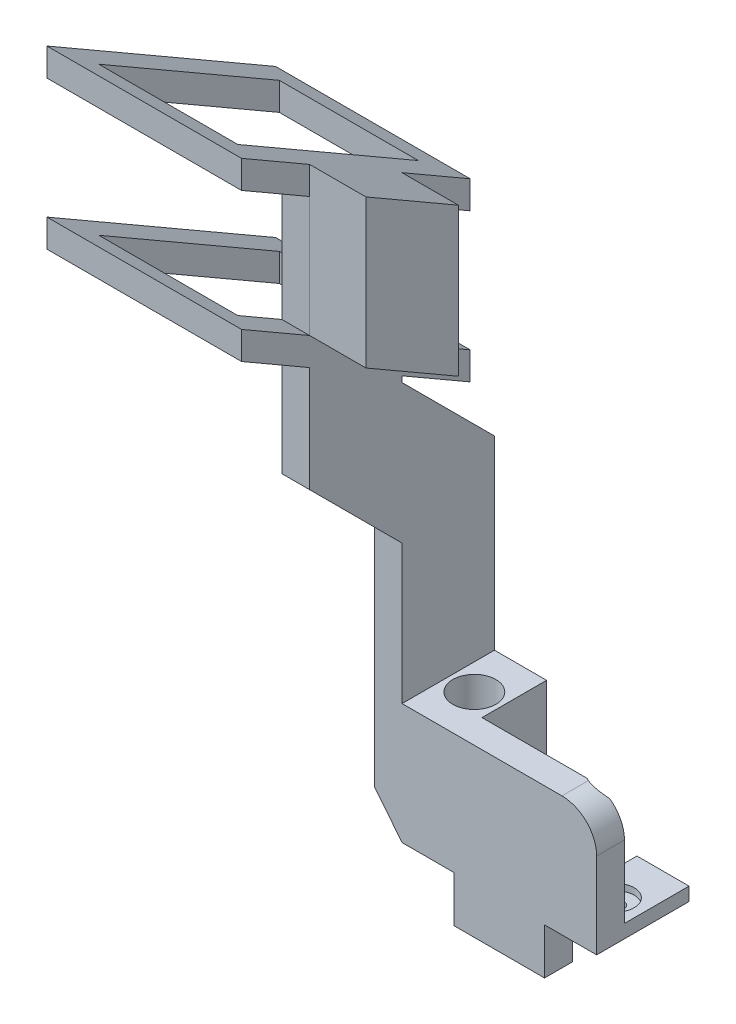
SolidWorks part; units mm, degrees
ref_plane "Front Plane" through (0, 0, 0) normal (0, 0, 1) x (1, 0, 0)
ref_plane "Top Plane" through (0, 0, 0) normal (0, 1, 0) x (1, 0, 0)
ref_plane "Right Plane" through (0, 0, 0) normal (1, 0, 0) x (0, 0, -1)
sketch "Sketch1" plane through (0, 0, 0) normal (0, 1, 0) x (1, 0, 0)
  line L1 (2.6118, 0) -> (10.109, 0)
  line L2 (2.6118, 0) -> (2.6118, -13.3)
  line L3 (2.6118, -13.3) -> (10.109, -13.3)
  line L4 (10.109, 0) -> (10.109, -13.3)
  line L5 (23.1146, -13.3) -> (30.6118, -13.3)
  line L6 (23.1146, -13.3) -> (23.1146, 0)
  line L7 (23.1146, 0) -> (30.6118, 0)
  line L8 (30.6118, -13.3) -> (30.6118, 0)
  circle A0 centre (6.3604, -6.65) radius 1
  circle A1 centre (26.8632, -6.65) radius 1
  point P20 (6.3604, 0)
  point P21 (2.6118, -6.65)
  point P22 (26.8632, 0)
  point P23 (30.6118, -6.65)
  dimension "D1" = 2
  dimension "D2" = 2
extrude "Boss-Extrude1" add sketch "Sketch1" along normal blind 2
sketch "Sketch2" plane through (0, 2, 0) normal (0, 1, 0) x (1, 0, 0)
  line L1 (2.6118, -13.3) -> (10.109, -13.3)
  line L2 (2.6118, -13.3) -> (2.6118, 0)
  line L3 (2.6118, 0) -> (10.109, 0)
  line L4 (10.109, -13.3) -> (10.109, 0)
sketch "Sketch3" plane through (0, 2, 0) normal (0, 1, 0) x (1, 0, 0)
  circle A0 centre (26.8632, -6.65) radius 2.5
  circle A1 centre (6.3604, -6.65) radius 2.5
  dimension "D1" = 5
  dimension "D2" = 5
extrude "Cut-Extrude1" cut sketch "Sketch3" against normal blind 1
sketch "Sketch4" plane through (0, 0, 13.3) normal (0, 0, 1) x (1, 0, 0)
  line L0 (10.109, 0) -> (10.109, -6.6258)
  line L1 (10.109, -6.6258) -> (23.1146, -6.6258)
  line L2 (23.1146, -6.6258) -> (23.1146, 2)
  line L3 (23.1146, 2) -> (10.109, 2)
  line L4 (10.109, 2) -> (10.109, 0)
extrude "Boss-Extrude3" add sketch "Sketch4" against normal blind 1
sketch "Sketch5" plane through (0, 2, 0) normal (0, 1, 0) x (1, 0, 0)
  line L0 (2.6118, 0) -> (2.6118, -13.3) construction
  line L1 (10.109, 0) -> (2.6118, 0)
  line L2 (10.109, 0) -> (10.109, -4)
  line L4 (2.6118, 0) -> (2.6118, -4)
  line L5 (23.1146, -12.3) -> (10.109, -12.3) construction
  line L6 (30.6118, -13.3) -> (2.6118, -13.3)
  line L7 (30.6118, -13.3) -> (30.6118, -12.3)
  line L8 (23.1146, -12.3) -> (10.109, -12.3)
  line L9 (2.6118, -13.3) -> (2.6118, -12.3)
  line L10 (10.109, -12.3) -> (10.109, 0) construction
  line L12 (2.6118, -12.3) -> (2.6118, -9.3)
  line L14 (10.109, -12.3) -> (10.109, -9.3)
  line L15 (30.6118, -13.3) -> (30.6118, 0) construction
  line L17 (23.1146, -12.3) -> (23.1146, -9.3)
  line L19 (30.6118, -12.3) -> (30.6118, -9.3)
  line L20 (23.1146, 0) -> (23.1146, -12.3) construction
  line L21 (30.6118, 0) -> (23.1146, 0)
  line L22 (30.6118, 0) -> (30.6118, -4)
  line L24 (23.1146, 0) -> (23.1146, -4)
  line L25 (2.6118, -4) -> (2.6118, -9.3)
  line L26 (10.109, -4) -> (10.109, -9.3)
  line L27 (23.1146, -4) -> (23.1146, -9.3)
  line L28 (30.6118, -4) -> (30.6118, -9.3)
  circle A0 centre (6.3604, -6.65) radius 3.1
  circle A1 centre (26.8632, -6.65) radius 3.1
  dimension "D5" = 6.2
  dimension "D6" = 6.2
  dimension "D1" = 4
  dimension "D2" = 3
  dimension "D3" = 3
  dimension "D4" = 4
extrude "Boss-Extrude4" add sketch "Sketch5" along normal up to surface (15.3233 mm away)
sketch "Sketch6" plane through (30.6118, 0, 0) normal (1, 0, 0) x (0, 0, -1)
  line L3 (-9.3, 17.3233) -> (0, 17.3233)
  line L5 (0, 17.3233) -> (0, 0) construction
  line L7 (0, 3.9257) -> (-9.3, 3.9257)
  line L8 (-9.3, 17.3233) -> (-9.3, 3.9257)
  line L10 (0, 17.3233) -> (0, 3.9257)
extrude "Cut-Extrude2" cut sketch "Sketch6" against normal up to surface (7.4972 mm away) up to face at (23.1146, 8.6616, 6.15)
sketch "Sketch7" plane through (0, 17.3233, 0) normal (0, 1, 0) x (1, 0, 0)
  line L0 (28.4718, -9.3) -> (30.6118, -9.3)
  line L1 (10.109, -13.3) -> (30.6118, -13.3)
  line L2 (10.109, -13.3) -> (10.109, -9.3)
  line L3 (10.109, -9.3) -> (25.2546, -9.3)
  line L4 (30.6118, -13.3) -> (30.6118, -9.3)
  arc A0 (25.2546, -9.3) -> (28.4718, -9.3) centre (26.8632, -6.65) ccw
extrude "Boss-Extrude5" add sketch "Sketch7" against normal up to surface (13.3976 mm away) up to face at (26.8632, 3.9257, 5.2417)
sketch "Sketch8" plane through (0, 3.9257, 0) normal (0, -1, 0) x (1, 0, 0)
  line L1 (10.109, 9.3) -> (23.1146, 9.3)
  line L2 (10.109, 9.3) -> (10.109, 12.3)
  line L3 (10.109, 12.3) -> (23.1146, 12.3)
  line L4 (23.1146, 9.3) -> (23.1146, 12.3)
extrude "Boss-Extrude6" add sketch "Sketch8" along normal through all
sketch "Sketch9" plane through (2.6118, 0, 0) normal (-1, 0, 0) x (0, 0, 1)
  line L0 (13.3, 17.3233) -> (13.3, 0) construction
  line L1 (0, 17.3233) -> (13.3, 17.3233)
  line L2 (0, 17.3233) -> (0, 5)
  line L3 (0, 5) -> (13.3, 5)
  line L4 (13.3, 17.3233) -> (13.3, 5)
  line L5 (0, 0) -> (13.3, 0) construction
  dimension "D1" = 5
extrude "Boss-Extrude7" add sketch "Sketch9" along normal blind 4
sketch "Sketch10" plane through (0, 17.3233, 0) normal (0, 1, 0) x (1, 0, 0)
  line L1 (-1.3882, 0) -> (2.6118, 0)
  line L2 (-1.3882, 0) -> (-1.3882, -13.3)
  line L3 (-1.3882, -13.3) -> (2.6118, -13.3)
  line L4 (2.6118, 0) -> (2.6118, -13.3)
extrude "Boss-Extrude8" add sketch "Sketch10" along normal blind 70
sketch "Sketch11" plane through (0, 0, 13.3) normal (0, 0, 1) x (1, 0, 0)
  line L0 (-1.3882, 5) -> (2.6118, 0)
  line L1 (2.6118, 0) -> (2.6118, 5)
  line L2 (2.6118, 5) -> (-1.3882, 5)
extrude "Boss-Extrude9" add sketch "Sketch11" against normal up to surface (13.3 mm away) up to face at (3.4861, 27.4116, 0)
sketch "Sketch15" plane through (0, 0, 13.3) normal (0, 0, 1) x (1, 0, 0)
  line L0 (-1.3882, 5) -> (-1.3882, 87.3233) construction
  line L1 (-1.3882, 57.3233) -> (2.6118, 57.3233)
  line L2 (-1.3882, 57.3233) -> (-1.3882, 37.3233)
  line L3 (-1.3882, 37.3233) -> (2.6118, 37.3233)
  line L4 (2.6118, 57.3233) -> (2.6118, 37.3233)
  line L5 (2.6118, 87.3233) -> (2.6118, 17.3233) construction
  line L6 (-1.3882, 87.3233) -> (2.6118, 87.3233) construction
  dimension "D1" = 20
  dimension "D2" = 30
extrude "Boss-Extrude13" add sketch "Sketch15" along normal blind 20
sketch "Sketch16" plane through (0, 57.3233, 0) normal (0, 1, 0) x (1, 0, 0)
  line L1 (-1.3882, -13.3) -> (2.6118, -13.3)
  line L2 (-1.3882, -13.3) -> (-1.3882, -33.3)
  line L3 (-1.3882, -33.3) -> (2.6118, -33.3)
  line L4 (2.6118, -13.3) -> (2.6118, -33.3)
extrude "Boss-Extrude14" add sketch "Sketch16" along normal up to surface (30 mm away) up to face at (0.6118, 87.3233, 6.65)
sketch "Sketch17" plane through (-1.3882, 0, 0) normal (-1, 0, 0) x (0, 0, 1)
  line L1 (0, 87.3233) -> (13.3, 87.3233)
  line L2 (0, 87.3233) -> (0, 57.3233)
  line L4 (13.3, 87.3233) -> (13.3, 57.3233)
  line L5 (0, 87.3233) -> (33.3, 87.3233) construction
  line L6 (33.3, 37.3233) -> (26.6, 37.3233)
  line L7 (33.3, 37.3233) -> (33.3, 87.3233)
  line L8 (33.3, 87.3233) -> (26.6, 87.3233)
  line L9 (26.6, 50.6233) -> (26.6, 87.3233)
  line L11 (13.3, 5) -> (13.3, 37.3233) construction
  line L12 (13.3, 57.3233) -> (63.724, 57.3233) construction
  line L13 (33.3, 37.3233) -> (-38.679, 37.3233) construction
  line L14 (13.3, 37.3233) -> (26.6, 50.6233)
  line L15 (13.3, 57.3233) -> (0, 44.0233)
  line L16 (0, 87.3233) -> (0, 5) construction
  line L17 (0, 57.3233) -> (0, 44.0233)
  line L18 (13.3, 37.3233) -> (33.3, 37.3233)
  line M13 (33.3, 37.3233) -> (33.3, 87.3233)
  line M14 (33.3, 87.3233) -> (0, 87.3233)
  line M15 (0, 87.3233) -> (0, 5)
  line M18 (13.3, 37.3233) -> (33.3, 37.3233)
  dimension "D2" = 13.3
  dimension "D3" = 13.3
extrude "Cut-Extrude3" cut sketch "Sketch17" against normal blind 20 contours L15 L4 M14 M15 | L14 L9 M18 M13 M14 region at (-1.3882, 58.0275, 28.3243) region at (-1.3882, 68.7972, 6.2478)
sketch "Sketch18" plane through (-1.3882, 0, 0) normal (-1, 0, 0) x (0, 0, 1)
  line L0 (13.3, 76.6685) -> (26.6, 76.6685) construction
  line L1 (3.4955, 77.8233) -> (36.4045, 96.8233)
  line L2 (3.4955, 77.8233) -> (3.4955, 73.8233)
  line L3 (3.4955, 73.8233) -> (36.4045, 92.8233)
  line L4 (36.4045, 96.8233) -> (36.4045, 92.8233)
  line L5 (3.4955, 56.5028) -> (36.4045, 75.5028)
  line L6 (3.4955, 56.5028) -> (3.4955, 52.5028)
  line L7 (3.4955, 52.5028) -> (36.4045, 71.5028)
  line L8 (36.4045, 75.5028) -> (36.4045, 71.5028)
  line L11 (19.95, 87.3233) -> (19.95, 58.3974) construction
  line L15 (13.3, 87.3233) -> (26.6, 87.3233) construction
  point P10 (19.95, 87.3233)
  point P11 (19.95, 66.0028)
  dimension "D1" = 4
  dimension "D2" = 4
  dimension "D3" = 15
  dimension "D4" = 38
  dimension "D5" = 38
extrude "Boss-Extrude15" add sketch "Sketch18" against normal blind 4
sketch "Sketch19" plane through (-1.3882, 0, 0) normal (-1, 0, 0) x (0, 0, 1)
  line L1 (3.4955, 77.8233) -> (6.9596, 79.8233)
  line L2 (3.4955, 77.8233) -> (3.4955, 73.8233)
  line L3 (3.4955, 73.8233) -> (6.9596, 75.8233)
  line L4 (6.9596, 79.8233) -> (6.9596, 75.8233)
  line L6 (3.4955, 56.5028) -> (6.9596, 58.5028)
  line L7 (3.4955, 56.5028) -> (3.4955, 52.5028)
  line L8 (3.4955, 52.5028) -> (6.9596, 54.5028)
  line L9 (6.9596, 58.5028) -> (6.9596, 54.5028)
  line L11 (36.4045, 75.5028) -> (32.9404, 73.5028)
  line L12 (36.4045, 75.5028) -> (36.4045, 71.5028)
  line L13 (36.4045, 71.5028) -> (32.9404, 69.5028)
  line L14 (32.9404, 73.5028) -> (32.9404, 69.5028)
  line L16 (36.4045, 92.8233) -> (32.9404, 90.8233)
  line L17 (36.4045, 92.8233) -> (36.4045, 96.8233)
  line L18 (36.4045, 96.8233) -> (32.9404, 94.8233)
  line L19 (32.9404, 90.8233) -> (32.9404, 94.8233)
  line L21 (3.4955, 56.5028) -> (3.4955, 52.5028) construction
  line L22 (13.3, 83.4839) -> (3.4955, 77.8233) construction
  line L23 (3.4955, 73.8233) -> (13.3, 79.4839) construction
  line L24 (13.3, 62.1634) -> (3.4955, 56.5028) construction
  line L25 (3.4955, 52.5028) -> (13.3, 58.1634) construction
  line L26 (26.6, 65.8422) -> (36.4045, 71.5028) construction
  line L27 (36.4045, 75.5028) -> (26.6, 69.8422) construction
  line L28 (26.6, 87.1627) -> (36.4045, 92.8233) construction
  line L29 (36.4045, 96.8233) -> (19.95, 87.3233) construction
  dimension "D1" = 4
  dimension "D2" = 4
  dimension "D3" = 4
  dimension "D4" = 4
  dimension "D5" = 4
extrude "Boss-Extrude16" add sketch "Sketch19" along normal blind 20
sketch "Sketch21" plane through (0, 3.9257, 0) normal (0, 1, 0) x (1, 0, 0)
  line L1 (23.1146, 0) -> (30.6118, 0)
  line L2 (23.1146, 0) -> (23.1146, -9.3)
  line L3 (23.1146, -9.3) -> (30.6118, -9.3)
  line L4 (30.6118, 0) -> (30.6118, -9.3)
extrude "Cut-Extrude4" cut sketch "Sketch21" against normal blind 2
sketch "Sketch22" plane through (-21.3882, 0, 0) normal (-1, 0, 0) x (0, 0, 1)
  line L0 (3.4955, 77.8233) -> (36.4045, 96.8233)
  line L1 (36.4045, 96.8233) -> (36.4045, 92.8233)
  line L2 (36.4045, 92.8233) -> (3.4955, 73.8233)
  line L3 (3.4955, 73.8233) -> (3.4955, 77.8233)
  line L4 (3.4955, 56.5028) -> (3.4955, 52.5028)
  line L5 (3.4955, 52.5028) -> (36.4045, 71.5028)
  line L6 (36.4045, 71.5028) -> (36.4045, 75.5028)
  line L7 (36.4045, 75.5028) -> (3.4955, 56.5028)
extrude "Boss-Extrude18" add sketch "Sketch22" along normal blind 4
sketch "Sketch23" plane through (2.6118, 0, 0) normal (1, 0, 0) x (0, 0, -1)
  line L0 (-13.3, 87.3233) -> (-13.3, 83.4839)
  line L1 (-13.3, 83.4839) -> (-19.95, 87.3233)
  line L2 (-19.95, 87.3233) -> (-13.3, 87.3233)
extrude "Cut-Extrude5" cut sketch "Sketch23" against normal blind 4
sketch "Sketch24" plane through (2.6118, 0, 0) normal (1, 0, 0) x (0, 0, -1)
  line L0 (-26.6, 91.1627) -> (-13.3003, 83.4841)
  line L1 (-26.6, 91.1627) -> (-26.5997, 69.842)
  line L2 (-13.3003, 83.4841) -> (-13.3, 62.1634)
  line L3 (-26.5997, 69.842) -> (-13.3, 62.1634)
  line L4 (-36.4045, 96.8233) -> (-3.4955, 77.8233) construction
  line L5 (-13.3, 79.4839) -> (-13.3, 62.1634) construction
extrude "Boss-Extrude20" add sketch "Sketch24" along normal blind 8.1
fillet "Fillet1" radius 5 1 edges at (30.6118, 17.3233, 11.3)
